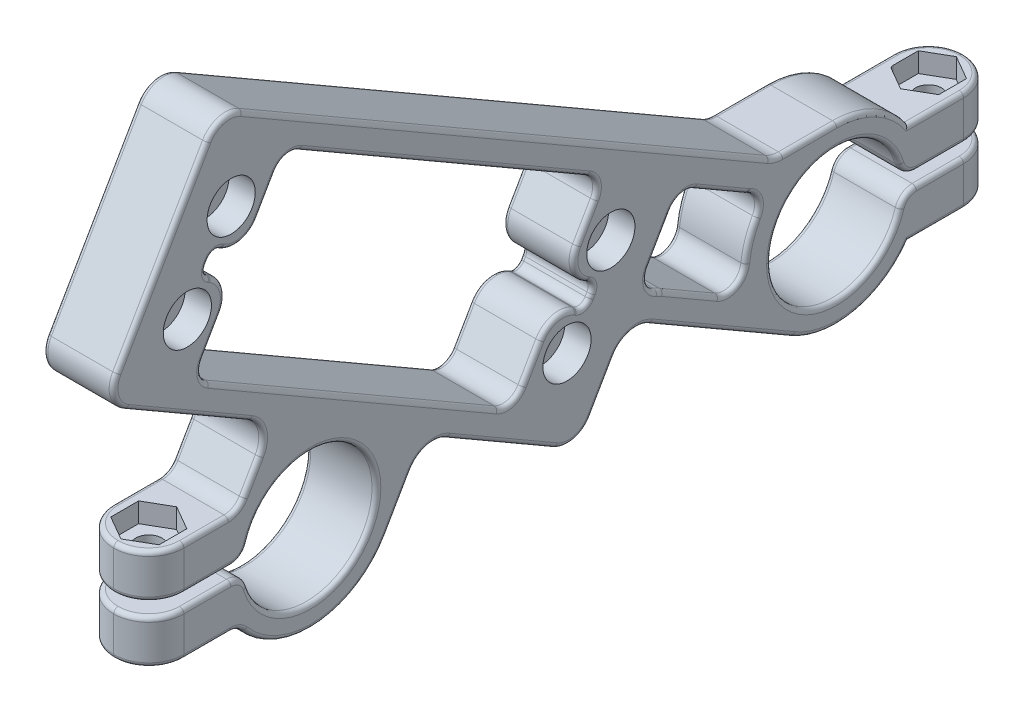
SolidWorks part; units mm, degrees
note: The reader was unsure of these and kept them because the rebuilt part matched: shared geometry of "Sketch6<2>".
ref_plane "Front Plane" through (0, 0, 0) normal (0, 0, 1) x (1, 0, 0)
ref_plane "Top Plane" through (0, 0, 0) normal (0, 1, 0) x (1, 0, 0)
ref_plane "Right Plane" through (0, 0, 0) normal (1, 0, 0) x (0, 0, -1)
sketch "Sketch1" plane through (0, 0, 0) normal (1, 0, 0) x (0, 0, -1)
  line L0 (0, 0) -> (-30, 0) construction
  line L1 (0, 0) -> (1.0395, 0) construction
  line L2 (0, 0) -> (30, 0) construction
  line L3 (-43.2301, 21.1232) -> (-6.8571, 0.1232)
  line L4 (-40.3314, 46.5851) -> (23.0359, 10)
  line L5 (23.0359, 10) -> (40, 10)
  line L6 (40, 10) -> (40, -10)
  line L7 (40, -10) -> (27.3205, -10)
  line L8 (-6.8571, 0.1232) -> (3.3929, 17.8768)
  line L9 (3.3929, 17.8768) -> (-32.9801, 38.8768)
  line L10 (-32.9801, 38.8768) -> (-43.2301, 21.1232)
  line L11 (-38.1051, 30) -> (-1.7321, 9) construction
  line L12 (-29.4449, 25) -> (-32.2021, 20.2243) construction
  line L13 (0, 0) -> (0, 71) construction
  line L14 (-29.4449, 25) -> (-29.4449, -7.5535) construction
  line L15 (-32.9801, 38.8768) -> (-39.2333, 42.487) construction
  line L16 (-39.2333, 42.487) -> (-49.4833, 24.7335) construction
  line L17 (-49.4833, 24.7335) -> (-43.2301, 21.1232) construction
  line L18 (-14.7936, 28.3768) -> (-14.6824, 28.5694) construction
  line L19 (-0.6039, -3.487) -> (-6.8571, 0.1232) construction
  line L20 (9.6461, 14.2665) -> (-0.6039, -3.487) construction
  line L21 (3.3929, 17.8768) -> (9.6461, 14.2665) construction
  line L22 (27.3205, -10) -> (6.1551, 2.2198)
  line L23 (6.1551, 2.2198) -> (0.4942, -7.5851)
  line L24 (0.4942, -7.5851) -> (-17.0006, 2.5155)
  line L25 (-17.0006, 2.5155) -> (-24.2265, -10)
  line L26 (-24.2265, -10) -> (-40, -10)
  line L27 (-40, -10) -> (-40, 2.6795)
  line L28 (-39.4449, 15.4737) -> (-53.5814, 23.6354)
  line L29 (-53.5814, 23.6354) -> (-40.3314, 46.5851)
  line L30 (-39.4449, 15.4737) -> (-34.3212, 12.5155)
  line L31 (-34.3212, 12.5155) -> (-40, 2.6795)
  line L32 (-37.5, 0) -> (37.5, 0) construction
  circle A0 centre (-30, 0) radius 7.5
  circle A1 centre (30, 0) radius 7.5
  circle A2 centre (-29.4449, 25) radius 13.5 construction
  circle A3 centre (-29.4449, 25) radius 12.25 construction
  circle A4 centre (0, 71) radius 42.5 construction
  circle A5 centre (0, 71) radius 41.25 construction
  circle A6 centre (0, 71) radius 38.75 construction
  circle A7 centre (-39.0692, 36.3301) radius 1.5
  circle A8 centre (4.2321, 11.3301) radius 1.5
  circle A9 centre (-0.7679, 2.6699) radius 1.5
  circle A10 centre (-44.0692, 27.6699) radius 1.5
  dimension "D3" = 30
  dimension "D5" = 10
  dimension "D7" = 27
  dimension "D8" = 71
  dimension "D12" = 77.5
  dimension "D13" = 82.5
  dimension "D14" = 85
  dimension "D28" = 3
  dimension "D30" = 15
  dimension "D31" = 75
  dimension "D1" = 30
  dimension "D2" = 30
  dimension "D4" = 42
  dimension "D6" = 10.25
  dimension "D9" = 38
  dimension "D10" = 25
  dimension "D11" = 3
  dimension "D15" = 3
  dimension "D16" = 3
  dimension "D17" = 10
  dimension "D18" = 10
  dimension "D19" = 10
  dimension "D20" = 3
  dimension "D21" = 3
  dimension "D22" = 10
  dimension "D23" = 10
  dimension "D24" = 10
  dimension "D25" = 10
  dimension "D26" = 25
  dimension "D27" = 5
  dimension "D29" = 10
extrude "Boss-Extrude1" add sketch "Sketch1" along normal blind 8
fillet "Fillet1" radius 3 3 edges at (4, 23.6354, 53.5814) (4, 46.5851, 40.3314) (4, -7.5851, -0.4942)
fillet "Fillet2" radius 10 6 edges at (4, -10, 40) (4, -10, 24.2265) (4, 10, -40) (4, -10, -40) (4, -10, -27.3205) (4, 2.6795, 40)
fillet "Fillet3" radius 3 4 edges at (4, 10, -23.0359) (4, 2.2198, -6.1551) (4, 2.5155, 17.0006) (4, 12.5155, 34.3212)
sketch "Sketch3" plane through (8, 0, 0) normal (1, 0, 0) x (0, 0, -1)
  line L0 (-38.1051, 30) -> (-1.7321, 9) construction
  line L1 (-32.9801, 38.8768) -> (-43.2301, 21.1232) construction
  line L2 (-6.8571, 0.1232) -> (3.3929, 17.8768) construction
  line L3 (-41.1424, 33.1392) -> (2.5053, 7.9392)
  line L4 (2.5053, 7.9392) -> (1.3053, 5.8608)
  line L5 (1.3053, 5.8608) -> (-42.3424, 31.0608)
  line L6 (-42.3424, 31.0608) -> (-41.1424, 33.1392)
  dimension "D1" = 1.2
  dimension "D2" = 1.2
  dimension "D3" = 4.2
  dimension "D4" = 4.2
extrude "Cut-Extrude2" cut sketch "Sketch3" against normal blind 10
sketch "Sketch2" plane through (8, 0, 0) normal (1, 0, 0) x (0, 0, -1)
  line L0 (7.2532, 4.1218) -> (12.0999, 12.5165)
  line L1 (19.7983, 8.0718) -> (12.0999, 12.5165)
  line L2 (-1.1321, 10.0392) -> (3.3929, 17.8768) construction
  line L3 (1.9942, -4.987) -> (4.6551, -0.3782) construction
  line L4 (19.7983, 8.0718) -> (22.1738, 7)
  line L42 (26.5, -6.0622) -> (10.2532, 3.3179)
  line L43 (19.7223, -2.1491) -> (10.2532, 3.3179)
  arc A22 (10.2532, 3.3179) -> (2.057, 1.1218) centre (7.2532, -1.8782) ccw
  arc A23 (10.2532, 3.3179) -> (7.2532, 4.1218) centre (7.2532, -1.8782) ccw
  circle A25 centre (30, 0) radius 10.5
  arc A26 (22.1738, 7) -> (19.7223, -2.1491) centre (30, 0) ccw
  dimension "D4" = 0
  dimension "D2" = 3
  dimension "D3" = 3
extrude "Cut-Extrude1" cut sketch "Sketch2" against normal mid plane 20
fillet "Fillet7" radius 2 5 edges at (4, -2.1491, -19.7223) (4, 4.1218, -7.2532) (4, 12.5165, -12.0999) (4, 8.0718, -19.7983) (4, 7, -22.1738)
fillet "Fillet8" radius 2 4 edges at (4, 17.8768, -3.3929) (4, 0.1232, 6.8571) (4, 21.1232, 43.2301) (4, 38.8768, 32.9801)
fillet "Fillet9" radius 3 4 edges at (4, 10.0392, 1.1321) (4, 7.9608, 2.3321) (4, 28.9608, 38.7051) (4, 31.0392, 37.5051)
fillet "Fillet10" radius 1 4 edges at (4, 5.8608, -1.3053) (4, 7.9392, -2.5053) (4, 31.0608, 42.3424) (4, 33.1392, 41.1424)
sketch "Sketch4" plane through (8, 0, 0) normal (1, 0, 0) x (0, 0, -1)
  line L0 (-30, 0) -> (-14.1758, 0) construction
  line L2 (-43.5173, -0.75) -> (-43.5173, 0.75)
  line L3 (-43.5173, 0.75) -> (-33.6333, 0.75)
  line L4 (-33.6333, 0.75) -> (-33.6333, -0.75)
  line L5 (-43.5173, -0.75) -> (-33.6333, -0.75)
  line L7 (-41.4981, 20.1232) -> (-8.5891, 1.1232) construction
  point P10 (-33.6333, 0)
  point P11 (-43.5173, 0)
  dimension "D1" = 1.5
  dimension "D2" = 30
extrude "Cut-Extrude3" cut sketch "Sketch4" against normal blind 10
ref_plane "Plane1" through (0, 6, -3.4641) normal (0, -0.866, 0.5) x (-1, 0, 0)
ref_plane "Plane2" through (0, 0, 0) normal (0, -1, 0) x (-1, 0, 0)
sketch "Sketch6" plane through (0, 0, 0) normal (0, -1, 0) x (-1, 0, 0)
  line L1 (0, -50.9833) -> (0, -36.9192) construction
  line L2 (-8, -37.4624) -> (-8, -39.9718)
  line L3 (-8, -37.4624) -> (-8, -39.9718) construction
  line L4 (-8, -37.4624) -> (0, -37.4624)
  line L5 (-8, -37.4624) -> (-8, -48.4624)
  line L6 (-8, -48.4624) -> (0, -48.4624)
  line L7 (0, -37.4624) -> (0, -48.4624)
  line L8 (-4, -37.4624) -> (-4, -44.4624) construction
  circle A0 centre (-4, -44.4624) radius 1.5
  dimension "D2" = 11
  dimension "D3" = 7
  dimension "D1" = 0
extrude "Boss-Extrude5" add sketch "Sketch6" along normal blind 5 from offset 0.75
extrude "Boss-Extrude6" add sketch "Sketch6<2>" against normal blind 5 from offset 0.75 offset against normal yes
sketch "Sketch6<2>" plane through (0, 0, 0) normal (0, -1, 0) x (-1, 0, 0) same geometry as "Sketch6"
sketch "Sketch7" plane through (0, 0, 0) normal (0, -1, 0) x (-1, 0, 0)
  line L1 (-4, -41.287) -> (-6.75, -42.8747)
  line L2 (-6.75, -42.8747) -> (-6.75, -46.0501)
  line L3 (-6.75, -46.0501) -> (-4, -47.6378)
  line L4 (-4, -47.6378) -> (-1.25, -46.0501)
  line L5 (-1.25, -46.0501) -> (-1.25, -42.8747)
  line L6 (-1.25, -42.8747) -> (-4, -41.287)
  circle A0 centre (-4, -44.4624) radius 2.75 construction
extrude "Cut-Extrude4" cut sketch "Sketch7" against normal blind 5 from offset 3.5 offset against normal yes
fillet "Fillet11" radius 4 4 edges at (8, -3.25, 48.4624) (0, -3.25, 48.4624) (0, 3.25, 48.4624) (8, 3.25, 48.4624)
fillet "Fillet12" radius 2 2 edges at (4, -5.75, 38.1815) (4, 5.75, 38.2272)
fillet "Fillet13" radius 2 2 edges at (4, -0.75, 37.4624) (4, 0.75, 37.4624)
sketch "Sketch8" plane through (0, 0, 0) normal (-1, 0, 0) x (0, 0, 1)
  line L0 (14.7936, 28.3768) -> (25.0436, 10.6232) construction
  line L1 (-0.7679, 11.3301) -> (-2.5, 14.3301)
  line L2 (-2.5, 14.3301) -> (-5.9641, 14.3301)
  line L3 (-5.9641, 14.3301) -> (-7.6962, 11.3301)
  line L4 (-7.6962, 11.3301) -> (-5.9641, 8.3301)
  line L5 (-5.9641, 8.3301) -> (-2.5, 8.3301)
  line L6 (-2.5, 8.3301) -> (-0.7679, 11.3301)
  line L7 (-1.6609, 18.8768) -> (31.2481, 37.8768) construction
  line L8 (41.4981, 20.1232) -> (8.5891, 1.1232) construction
  line L9 (6.5668, 11.7913) -> (33.2704, 27.2087) construction
  line L10 (37.3372, 33.3301) -> (35.6051, 36.3301)
  line L11 (40.8013, 33.3301) -> (37.3372, 33.3301)
  line L12 (42.5333, 36.3301) -> (40.8013, 33.3301)
  line L13 (40.8013, 39.3301) -> (42.5333, 36.3301)
  line L14 (37.3372, 39.3301) -> (40.8013, 39.3301)
  line L15 (35.6051, 36.3301) -> (37.3372, 39.3301)
  line L16 (2.5, 5.6699) -> (4.2321, 2.6699)
  line L17 (-0.9641, 5.6699) -> (2.5, 5.6699)
  line L18 (-2.6962, 2.6699) -> (-0.9641, 5.6699)
  line L19 (-0.9641, -0.3301) -> (-2.6962, 2.6699)
  line L20 (2.5, -0.3301) -> (-0.9641, -0.3301)
  line L21 (4.2321, 2.6699) -> (2.5, -0.3301)
  line L22 (42.3372, 30.6699) -> (40.6051, 27.6699)
  line L23 (45.8013, 30.6699) -> (42.3372, 30.6699)
  line L24 (47.5333, 27.6699) -> (45.8013, 30.6699)
  line L25 (45.8013, 24.6699) -> (47.5333, 27.6699)
  line L26 (42.3372, 24.6699) -> (45.8013, 24.6699)
  line L27 (40.6051, 27.6699) -> (42.3372, 24.6699)
  circle A0 centre (-4.2321, 11.3301) radius 3 construction
  point P24 (19.9186, 19.5)
extrude "Cut-Extrude5" cut sketch "Sketch8" against normal blind 2.5
sketch "Sketch9" plane through (8, 0, 0) normal (1, 0, 0) x (0, 0, -1)
  circle A0 centre (-0.7679, 2.6699) radius 2.75
  circle A1 centre (4.2321, 11.3301) radius 2.75
  circle A2 centre (-44.0692, 27.6699) radius 2.75
  circle A3 centre (-39.0692, 36.3301) radius 2.75
extrude "Cut-Extrude6" cut sketch "Sketch9" against normal blind 3
sketch "Sketch10" plane through (0, -5.75, 0) normal (0, -1, 0) x (1, 0, 0)
  circle A0 centre (4, 44.4624) radius 2.75
extrude "Cut-Extrude7" cut sketch "Sketch10" against normal blind 3
sketch "Sketch11" plane through (8, 0, 0) normal (1, 0, 0) x (0, 0, -1)
  line L0 (30, 0) -> (10.3558, 5.4956) construction
  line L1 (14.5939, 3.2716) -> (15.1327, 5.1976)
  line L2 (15.1327, 5.1976) -> (27.8104, 1.6509)
  line L3 (27.8104, 1.6509) -> (27.2716, -0.2751)
  line L4 (14.5939, 3.2716) -> (27.2716, -0.2751)
  point P9 (27.541, 0.6879)
  point P10 (14.8633, 4.2346)
  dimension "D1" = 2
extrude "Cut-Extrude8" [suppressed] cut sketch "Sketch11" against normal through all
fillet "Fillet14" [suppressed] radius 1
mirror "Mirror1" about plane through (0, 0, 0) normal (0, 0, 1) of "Cut-Extrude3", "Boss-Extrude5", "Boss-Extrude6", "Cut-Extrude4", "Fillet11", "Cut-Extrude7"
fillet "Fillet15" radius 2 2 edges at (4, 0.75, -37.4624) (4, -0.75, -37.4624)
fillet "Fillet16" radius 0.5 111 edges at (0, -5.9357, 38.3201) (0, -5.75, 41.8121) (1.1716, -5.75, 47.2908) (6.8284, -0.75, 47.2908) (0, -0.75, 41.7778) (0, -1.1441, 37.9012) (0, 1.1441, 37.9012) (0, 0.75, 41.7778) (1.1716, 0.75, 47.2908) (6.8284, 0.75, 47.2908) (0, 0.75, -41.7778) (1.1716, -0.75, -47.2908) (6.8284, -0.75, -47.2908) (0, 14.391, -1.3804) (0, 7.832, -2.1052) (0, 6.9, -1.9053) (0, 6.2609, -1.198) (0, 6.4108, -0.3526) (0, 6.7605, 2.0104) (0, 3.609, 4.8446) (0, 0.9234, 7.0715) (0, 10.6232, 25.0436) (0, 24.609, 41.2176) (0, 28.6392, 39.9054) (0, 30.5108, 41.3898) (0, 31.168, 41.9423) (0, 32.1, 41.7424) (0, 32.7391, 41.0352) (0, 32.5892, 40.1898) (0, 38.0766, 32.7657) (0, 11.7163, -12.3143) (0, 8.64, -9.8618) (0, 3.4956, -9.9219) (0, -0.3873, -18.4798) (0, 3.2482, -20.015) (0, 6.7974, -21.0348) (0, 8.0157, -19.9225) (0, 6.0179, 38.3819) (0, 8.3337, 36.7355) (0, 18.0755, 43.9513) (0, 23.9571, 52.3811) (0, 27.7435, 7.6968) (0, 10, -26.9199) (6.8284, 5.75, -47.2908) (1.1716, 5.75, -47.2908) (6.8284, -5.75, -47.2908) (1.1716, -5.75, -47.2908) (0, -8.6603, 25) (0, -2.5413, 19.9202) (0, 1.3152, 16.679) (0, -2.5348, 8.2532) (0, -6.3848, -0.1726) (0, -2.6826, -3.3247) (0, 1.0195, -6.4767) (0, -3.9702, -16.8766) (8, -1.1441, -37.9012) (8, -0.75, -41.7778) (8, -5.75, -41.322) (8, -8.8741, -34.6098) (8, -9.6593, -27.4118) (8, -3.9702, -16.8766) (8, 1.0195, -6.4767) (8, -6.3848, -0.1726) (8, 1.3152, 16.679) (8, -8.6603, 25) (8, -5.9357, 38.3201) (8, -5.75, 41.8121) (8, -0.75, 41.7778) (8, -1.1441, 37.9012) (8, 0, 22.5) (8, 1.1441, 37.9012) (8, 0.75, 41.7778) (8, 5.75, 41.9222) (8, 8.3337, 36.7355) (8, 12.1939, 35.5215) (8, 18.0755, 43.9513) (8, 45.3848, 40.0098) (8, 27.7435, 7.6968) (8, 10.1022, -23.0633) (8, 8.8741, -34.6098) (8, 5.75, -41.322) (8, 0.75, -41.7778) (8, 1.1441, -37.9012) (8, 0, -22.5) (0, 17.6623, -2.5928) (0, 9.8191, -16.7719) (0, 8.8741, -34.6098) (0, 5.75, -41.322) (1.25, 4.625, -42.8747) (0, -5.75, -41.322) (8, 21.3377, 42.4299) (8, 24.609, 41.2176) (8, 31.168, 41.9423) (8, 32.1, 41.7424) (8, 32.7391, 41.0352) (8, 32.5892, 40.1898) (8, 32.2395, 37.8267) (8, 35.391, 34.9926) (8, 17.6623, -2.5928) (8, 14.391, -1.3804) (8, 10.3608, -0.0682) (8, 8.4892, -1.5526) (8, 7.832, -2.1052) (8, 3.2482, -20.015) (8, 8.0157, -19.9225) (8, 8.074, -19.7994) (8, 9.8191, -16.7719) (8, 8.64, -9.8618) (8, 4.858, -8.4602) (8, 3.4956, -9.9219) (8, 1.492, -13.4158)
